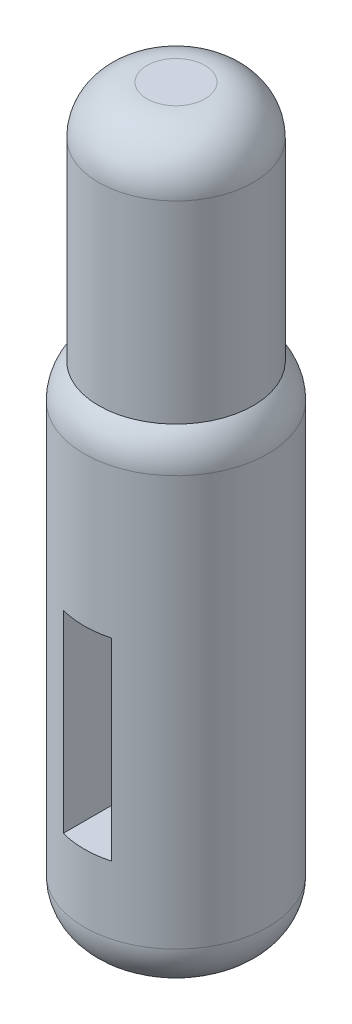
SolidWorks part; units mm, degrees
ref_plane "Front Plane" through (0, 0, 0) normal (0, 0, 1) x (1, 0, 0)
ref_plane "Top Plane" through (0, 0, 0) normal (0, 1, 0) x (1, 0, 0)
ref_plane "Right Plane" through (0, 0, 0) normal (1, 0, 0) x (0, 0, -1)
sketch "Sketch1" plane through (0, 0, 0) normal (0, 1, 0) x (1, 0, 0)
  circle A1 centre (0, 0) radius 19
extrude "Boss-Extrude3" add sketch "Sketch1" along normal blind 102
sketch "Sketch2" plane through (0, 102, 0) normal (0, 1, 0) x (1, 0, 0)
  circle A0 centre (0, 0) radius 16
extrude "Boss-Extrude4" add sketch "Sketch2" along normal blind 50
fillet "Fillet1" radius 10 1 edges at (0, 102, 19)
fillet "Fillet2" radius 10 1 edges at (0, 152, 16)
fillet "Fillet3" radius 10 1 edges at (0, 0, 19)
sketch "Sketch3" plane through (0, 0, 0) normal (0, 0, 1) x (1, 0, 0)
  line L0 (0, 152) -> (0, 0)
  line L1 (6, 152) -> (-6, 152) construction
  line L2 (0, 0) -> (0, 44)
  line L4 (-5, 64) -> (5, 64)
  line L5 (-5, 64) -> (-5, 24)
  line L6 (-5, 24) -> (5, 24)
  line L7 (5, 64) -> (5, 24)
  line L8 (-5, 64) -> (5, 24) construction
  line L9 (-5, 24) -> (5, 64) construction
extrude "Cut-Extrude1" cut sketch "Sketch3" against normal through all and the other way through all contours L5 L6 L7 L4
